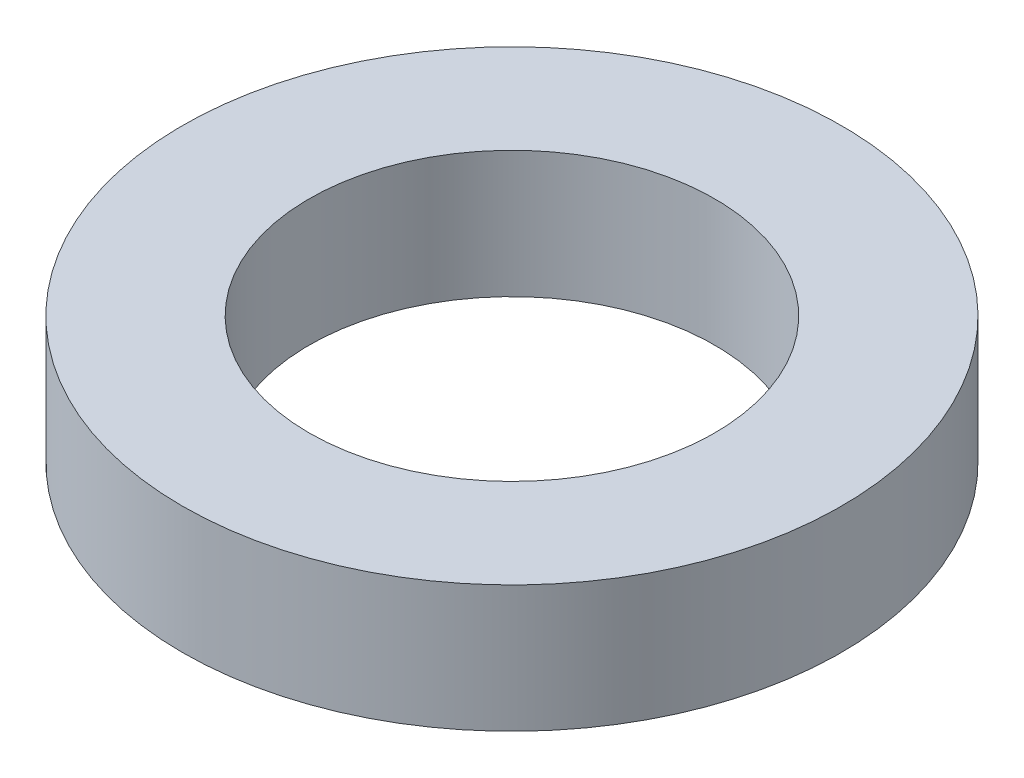
SolidWorks part; units mm, degrees
ref_plane "Front Plane" through (0, 0, 0) normal (0, 0, 1) x (1, 0, 0)
ref_plane "Top Plane" through (0, 0, 0) normal (0, 1, 0) x (1, 0, 0)
ref_plane "Right Plane" through (0, 0, 0) normal (1, 0, 0) x (0, 0, -1)
sketch "Sketch1" plane through (0, 0, 0) normal (0, 1, 0) x (1, 0, 0)
  circle A0 centre (0, 0) radius 65
  dimension "FLANGE_OD" = 130
extrude "Boss-Extrude1" add sketch "Sketch1" along normal blind 25
sketch "Sketch2" plane through (0, 0, 0) normal (0, 1, 0) x (1, 0, 0)
  circle A0 centre (0, 0) radius 40
  dimension "BORE_D" = 80
extrude "Cut-Extrude1" cut sketch "Sketch2" along normal through all
sketch "Sketch3" plane through (0, 25, 0) normal (0, 1, 0) x (1, 0, 0)
  circle A0 centre (0, 0) radius 25.0821 construction
  circle A1 centre (-25.0821, 0) radius 2.1872
  dimension "BOLT_D" = 4.3744
  dimension "BOLT_PCD" = 50.1641
extrude "Cut-Extrude2" cut sketch "Sketch3" against normal blind 24.1307 rebuild error yes
pattern_circular "CirPattern1" count 5 over 360 rebuild error yes
